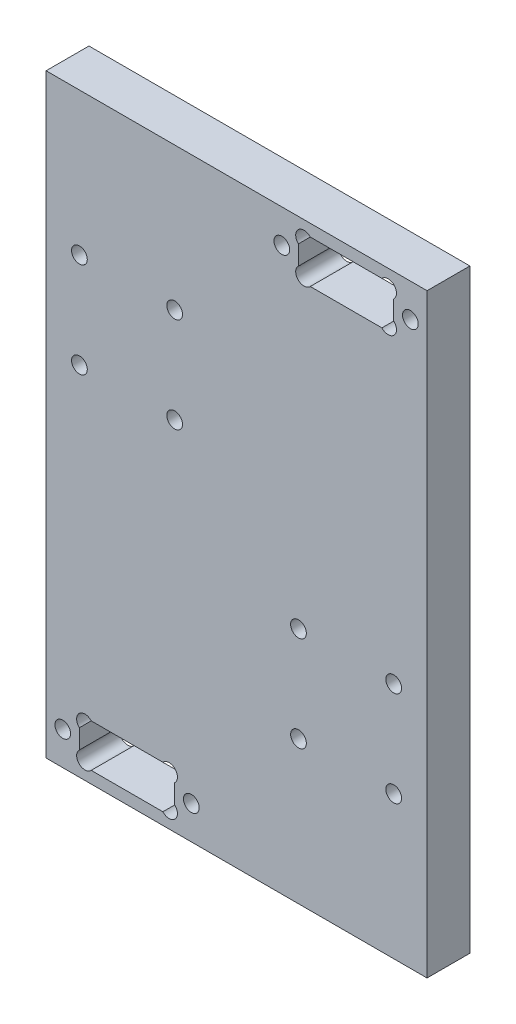
SolidWorks part; units mm, degrees
ref_plane "Plan de face" through (0, 0, 0) normal (0, 0, 1) x (1, 0, 0)
ref_plane "Plan de dessus" through (0, 0, 0) normal (0, 1, 0) x (1, 0, 0)
ref_plane "Plan de droite" through (0, 0, 0) normal (1, 0, 0) x (0, 0, -1)
sketch "Esquisse1" plane through (0, 0, 0) normal (0, 0, 1) x (1, 0, 0)
  line L1 (0, 0) -> (80, 0)
  line L2 (0, 0) -> (0, 125)
  line L3 (0, 125) -> (80, 125)
  line L4 (80, 0) -> (80, 125)
  dimension "D1" = 125
  dimension "D2" = 80
extrude "Boss.-Extru.1" add sketch "Esquisse1" along normal blind 9
sketch "Esquisse2" plane through (0, 0, 9) normal (0, 0, 1) x (1, 0, 0)
  line L0 (0, 0) -> (80, 0) construction
  line L1 (7, 11.5) -> (27, 11.5)
  line L2 (7, 11.5) -> (7, 2.5)
  line L3 (7, 2.5) -> (27, 2.5)
  line L4 (27, 11.5) -> (27, 2.5)
  line L5 (0, 125) -> (0, 0) construction
  line L6 (80, 125) -> (0, 125) construction
  line L7 (53, 122.5) -> (73, 122.5)
  line L8 (53, 122.5) -> (53, 113.5)
  line L9 (53, 113.5) -> (73, 113.5)
  line L10 (73, 122.5) -> (73, 113.5)
  line L11 (80, 0) -> (80, 125) construction
  dimension "D1" = 9
  dimension "D2" = 2.5
  dimension "D3" = 7
  dimension "D4" = 20
  dimension "D5" = 2.5
  dimension "D6" = 7
extrude "Enlèv. mat.-Extru.1" cut sketch "Esquisse2" against normal up to vertex (9 mm away) up to point (0, 0, 0)
sketch "Esquisse3" plane through (0, 0, 9) normal (0, 0, 1) x (1, 0, 0)
  line L0 (17, 11.5) -> (17, 2.5) construction
  line L1 (27, 11.5) -> (7, 11.5) construction
  line L2 (7, 2.5) -> (27, 2.5) construction
  line L3 (7, 7) -> (27, 7) construction
  line L4 (7, 11.5) -> (7, 2.5) construction
  line L5 (27, 2.5) -> (27, 11.5) construction
  line L6 (7, 9.0251) -> (9.4749, 11.5)
  line L7 (8.2374, 10.2626) -> (7, 11.5) construction
  line L8 (7, 11.5) -> (6.9293, 11.5707) construction
  line L9 (27, 11.5) -> (27.0707, 11.5707) construction
  line L10 (25.7626, 10.2626) -> (27, 11.5) construction
  line L11 (27, 9.0251) -> (24.5251, 11.5)
  line L12 (25.7626, 3.7374) -> (27, 2.5) construction
  line L13 (27, 2.5) -> (27.0707, 2.4293) construction
  line L14 (7, 2.5) -> (6.9293, 2.4293) construction
  line L15 (8.2374, 3.7374) -> (7, 2.5) construction
  line L16 (27, 4.9749) -> (24.5251, 2.5)
  line L17 (7, 4.9749) -> (9.4749, 2.5)
  line L18 (80, 62.5) -> (0, 62.5) construction
  line L19 (80, 0) -> (80, 125) construction
  line L20 (0, 125) -> (0, 0) construction
  line L21 (8.2374, 121.2626) -> (7, 122.5) construction
  line L22 (7, 122.5) -> (6.9293, 122.5707) construction
  line L23 (27, 122.5) -> (27.0707, 122.5707) construction
  line L24 (25.7626, 121.2626) -> (27, 122.5) construction
  line L25 (25.7626, 114.7374) -> (27, 113.5) construction
  line L26 (27, 113.5) -> (27.0707, 113.4293) construction
  line L27 (7, 113.5) -> (6.9293, 113.4293) construction
  line L28 (8.2374, 114.7374) -> (7, 113.5) construction
  line L29 (7, 118) -> (27, 118) construction
  line L30 (17, 113.5) -> (17, 122.5) construction
  line L31 (7, 120.0251) -> (9.4749, 122.5) construction
  line L32 (27, 120.0251) -> (24.5251, 122.5) construction
  line L33 (27, 115.9749) -> (24.5251, 113.5) construction
  line L34 (7, 115.9749) -> (9.4749, 113.5) construction
  line L35 (40, 62.5) -> (40, 125) construction
  line L36 (80, 125) -> (0, 125) construction
  line L37 (63, 113.5) -> (63, 122.5) construction
  line L38 (73, 118) -> (53, 118) construction
  line L39 (71.7626, 114.7374) -> (73, 113.5) construction
  line L40 (73, 113.5) -> (73.0707, 113.4293) construction
  line L41 (53, 113.5) -> (52.9293, 113.4293) construction
  line L42 (54.2374, 114.7374) -> (53, 113.5) construction
  line L43 (54.2374, 121.2626) -> (53, 122.5) construction
  line L44 (53, 122.5) -> (52.9293, 122.5707) construction
  line L45 (73, 122.5) -> (73.0707, 122.5707) construction
  line L46 (71.7626, 121.2626) -> (73, 122.5) construction
  line L47 (73, 115.9749) -> (70.5251, 113.5)
  line L48 (53, 115.9749) -> (55.4749, 113.5)
  line L49 (53, 120.0251) -> (55.4749, 122.5)
  line L50 (73, 120.0251) -> (70.5251, 122.5)
  line L51 (7, 7) -> (0, 7) construction
  arc A0 (7, 9.0251) -> (9.4749, 11.5) centre (8.1686, 10.3314) cw
  arc A1 (27, 9.0251) -> (24.5251, 11.5) centre (25.8314, 10.3314) ccw
  arc A2 (27, 4.9749) -> (24.5251, 2.5) centre (25.8314, 3.6686) cw
  arc A3 (7, 4.9749) -> (9.4749, 2.5) centre (8.1686, 3.6686) ccw
  arc A4 (7, 120.0251) -> (9.4749, 122.5) centre (8.1686, 121.3314) cw construction
  arc A5 (27, 120.0251) -> (24.5251, 122.5) centre (25.8314, 121.3314) ccw construction
  arc A6 (27, 115.9749) -> (24.5251, 113.5) centre (25.8314, 114.6686) cw construction
  arc A7 (7, 115.9749) -> (9.4749, 113.5) centre (8.1686, 114.6686) ccw construction
  arc A8 (73, 115.9749) -> (70.5251, 113.5) centre (71.8314, 114.6686) cw
  arc A9 (53, 115.9749) -> (55.4749, 113.5) centre (54.1686, 114.6686) ccw
  arc A10 (53, 120.0251) -> (55.4749, 122.5) centre (54.1686, 121.3314) cw
  arc A11 (73, 120.0251) -> (70.5251, 122.5) centre (71.8314, 121.3314) ccw
  circle A12 centre (3.5, 7) radius 1.65
  circle A13 centre (30.5, 7) radius 1.65
  circle A14 centre (30.5, 118) radius 1.65 construction
  circle A15 centre (3.5, 118) radius 1.65 construction
  circle A16 centre (49.5, 118) radius 1.65
  circle A17 centre (76.5, 118) radius 1.65
  dimension "D1" = 3.5
  dimension "D3" = 3.3
  dimension "D2" = 0.1
extrude "Enlèv. mat.-Extru.2" cut sketch "Esquisse3" against normal through all both and the other way through all
sketch "Esquisse4" plane through (0, 0, 9) normal (0, 0, 1) x (1, 0, 0)
  line L0 (17, 11.5) -> (17, 125) construction
  line L1 (24.5251, 11.5) -> (9.4749, 11.5) construction
  line L2 (80, 125) -> (0, 125) construction
  line L3 (40, 125) -> (40, 0) construction
  line L4 (0, 0) -> (80, 0) construction
  line L5 (17, 85) -> (0, 85) construction
  line L6 (0, 125) -> (0, 0) construction
  line L7 (40, 62.5) -> (0, 62.5) construction
  line L8 (17, 40) -> (0, 40) construction
  line L9 (63, 40) -> (80, 40) construction
  circle A0 centre (7, 95) radius 1.65
  circle A1 centre (27, 95) radius 1.65
  circle A2 centre (27, 75) radius 1.65
  circle A3 centre (7, 75) radius 1.65
  circle A4 centre (7, 50) radius 1.65 construction
  circle A5 centre (27, 50) radius 1.65 construction
  circle A6 centre (27, 30) radius 1.65 construction
  circle A7 centre (7, 30) radius 1.65 construction
  circle A8 centre (73, 30) radius 1.65
  circle A9 centre (53, 30) radius 1.65
  circle A10 centre (53, 50) radius 1.65
  circle A11 centre (73, 50) radius 1.65
  dimension "D2" = 20
  dimension "D3" = 20
  dimension "D4" = 3.3
  dimension "D1" = 40
extrude "Enlèv. mat.-Extru.3" cut sketch "Esquisse4" against normal up to vertex (9 mm away) up to point (0, 0, 0)
